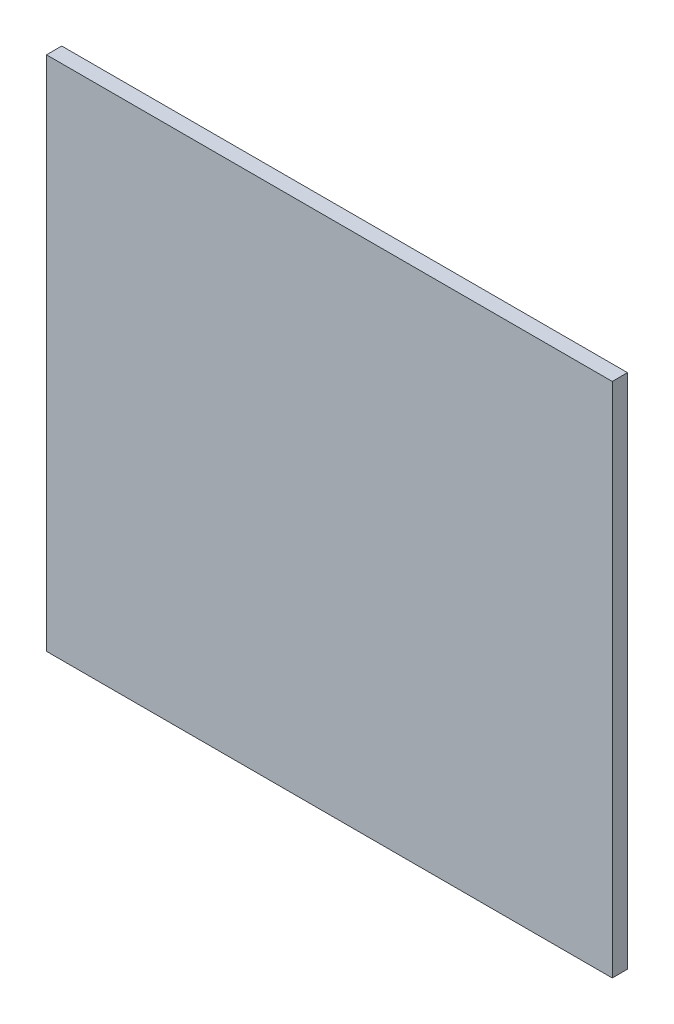
SolidWorks part; units mm, degrees
ref_plane "Front Plane" through (0, 0, 0) normal (0, 0, 1) x (1, 0, 0)
ref_plane "Top Plane" through (0, 0, 0) normal (0, 1, 0) x (1, 0, 0)
ref_plane "Right Plane" through (0, 0, 0) normal (1, 0, 0) x (0, 0, -1)
sketch "Sketch1" plane through (0, 0, 0) normal (0, 0, 1) x (1, 0, 0)
  line L1 (-167, -152.5) -> (167, -152.5)
  line L2 (-167, -152.5) -> (-167, 152.5)
  line L3 (-167, 152.5) -> (167, 152.5)
  line L4 (167, -152.5) -> (167, 152.5)
  line L5 (-167, -152.5) -> (167, 152.5) construction
  line L6 (-167, 152.5) -> (167, -152.5) construction
  point P0 (0, 0)
  dimension "D1" = 334
  dimension "D2" = 305
extrude "Boss-Extrude1" add sketch "Sketch1" along normal blind 9
equation "\"PCLength\"= 316mm'Length across I/O from PS to GPU"
equation "\"PCWidth\"= 242mm'Distance of longest part parallel to GPU(ussually GPU)"
equation "\"PCHeight\"= 178mm'Tallest point with mobo laying flat"
equation "\"WallThickness\"= 9mm'Thickness of each outer tank wall"
equation "\"ThermoBarrierThickness\"= 3mm'Thickness of barrier between hot side and cold side"
equation "\"HotSideGap\"= 25mm'Space in the hot side for a pump"
equation "\"PCClearance\"= 30mm'Clearance from top of tank to top of PC"
equation "\"RadiatorHeight\"= 275mm'Final Height from ground of radiators"
equation "\"D1@Sketch1\"=\"PCLength\" + (2 * \"WallThickness\")"
equation "\"D2@Sketch1\"=\"RadiatorHeight\" + \"PCClearance\""
equation "\"D1@Boss-Extrude1\"=\"WallThickness\""
